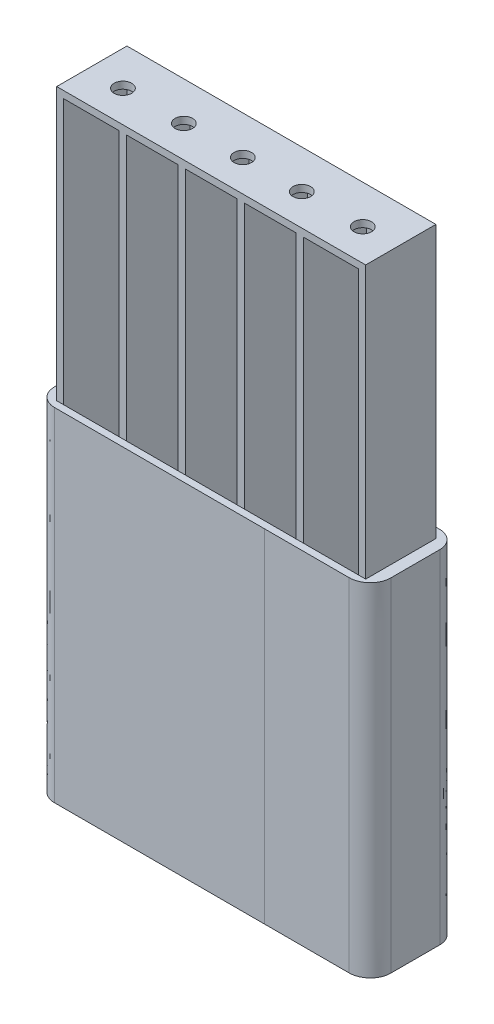
SolidWorks part; units mm, degrees
ref_plane "Front Plane" through (0, 0, 0) normal (0, 0, 1) x (1, 0, 0)
ref_plane "Top Plane" through (0, 0, 0) normal (0, 1, 0) x (1, 0, 0)
ref_plane "Right Plane" through (0, 0, 0) normal (1, 0, 0) x (0, 0, -1)
ref_plane "Plane1" through (0, 10, 0) normal (0, 1, 0) x (1, 0, 0)
sketch "Sketch1" plane through (0, 0, 0) normal (0, 0, 1) x (1, 0, 0)
  line L1 (-44, -87.5) -> (44, -87.5)
  line L2 (-44, -87.5) -> (-44, 87.5)
  line L3 (-44, 87.5) -> (44, 87.5)
  line L4 (44, -87.5) -> (44, 87.5)
  line L5 (-44, -87.5) -> (44, 87.5) construction
  line L6 (-44, 87.5) -> (44, -87.5) construction
  point P0 (0, 0)
  dimension "D1" = 88
  dimension "D2" = 175
extrude "Boss-Extrude1" add sketch "Sketch1" along normal blind 2
sketch "Sketch2" plane through (0, 0, 2) normal (0, 0, 1) x (1, 0, 0)
  line L4 (44, -87.5) -> (44, 87.5)
  line L5 (44, 87.5) -> (-44, 87.5)
  line L6 (-44, 87.5) -> (-44, -87.5)
  line L7 (-44, -87.5) -> (44, -87.5)
  line L8 (44, -87.5) -> (44, 87.5)
  line L9 (44, 87.5) -> (-44, 87.5)
  line L10 (-44, 87.5) -> (-44, -87.5)
  line L11 (-44, -87.5) -> (44, -87.5)
  dimension "D1" = 0
extrude "Extrude-Thin1" add sketch "Sketch2" along normal blind 18 thin thin type one direction reverse wall 2
sketch "Sketch7" plane through (0, 10, 0) normal (0, -1, 0) x (1, 0, 0)
  line L5 (-42.729, -2.8181) -> (42.1989, -2.8181)
  line L6 (47.2701, 2.1175) -> (47.2701, 16.0931)
  line L7 (41.1907, 22.0001) -> (17.1675, 21.99)
  line L8 (17.1675, 21.99) -> (-42.6899, 21.98)
  line L9 (-47.7299, 16.9812) -> (-47.7299, 2.1519)
  line L10 (-42.729, -2.8181) -> (42.1989, -2.8181)
  line L11 (47.2701, 2.1175) -> (47.2701, 16.0931)
  line L12 (41.1907, 22.0001) -> (17.1675, 21.99)
  line L13 (17.1675, 21.99) -> (-42.6899, 21.98)
  line L14 (-47.7299, 16.9812) -> (-47.7299, 2.1519)
  spline S4 degree 3 poles (-197.9292, 967.9227) (-37.6257, 170.0029) (18.1252, -7.458) (43.4954, -2.6664) (43.8136, -2.5749) (44.4247, -2.3335) (44.715, -2.1853) (45.2651, -1.8341) (45.5273, -1.6283) (45.9993, -1.1755) (46.2111, -0.9281) (46.4919, -0.5246) (46.5797, -0.3838) (46.7394, -0.0962) (46.8114, 0.0506) (47.0046, 0.5001) (47.1031, 0.8115) (53.1934, 30.3136) (-212.4086, 92.7702) (-718.1247, -641.4333) knots -9.650491 -9.650491 -9.650491 -9.650491 0.125 0.125 0.25 0.25 0.375 0.375 0.5 0.5 0.625 0.625 0.6875 0.6875 0.75 0.75 0.875 0.875 12.141398 12.141398 12.141398 12.141398 only from (42.1989, -2.8181) to (47.2701, 2.1175)
  spline S5 degree 3 poles (-921.5937, -231.4959) (-135.954, -70.0769) (52.7009, -9.9346) (47.1133, 17.4531) (47.0646, 17.6429) (46.9471, 18.0191) (46.8783, 18.2055) (46.6465, 18.7468) (46.4572, 19.0884) (46.1218, 19.5723) (46.0005, 19.7296) (45.7445, 20.0293) (45.6098, 20.1718) (45.1864, 20.5775) (44.8786, 20.8194) (44.2107, 21.2451) (43.8613, 21.4222) (43.1338, 21.7084) (42.7522, 21.8183) (5.7206, 28.7806) (-70.2801, -290.5664) (-187.4885, -951.498) knots -8.753519 -8.753519 -8.753519 -8.753519 0.125 0.125 0.1875 0.1875 0.25 0.25 0.375 0.375 0.4375 0.4375 0.5 0.5 0.625 0.625 0.75 0.75 0.875 0.875 12.708397 12.708397 12.708397 12.708397 only from (47.2701, 16.0931) to (41.1907, 22.0001)
  spline S6 degree 3 poles (193.8773, -949.635) (30.8282, -132.4012) (-20.3115, 26.4663) (-43.8283, 21.8535) (-43.9874, 21.8143) (-44.3027, 21.72) (-44.4596, 21.6646) (-44.9163, 21.4778) (-45.2053, 21.3253) (-45.7525, 20.9647) (-46.0122, 20.7545) (-46.4782, 20.2945) (-46.6874, 20.0434) (-46.9647, 19.6344) (-47.0511, 19.4923) (-47.2077, 19.2032) (-47.2785, 19.0556) (-47.4684, 18.6038) (-47.5657, 18.2894) (-53.7533, -12.2904) (224.8389, -73.2836) (932.5497, -180.6044) knots -8.978367 -8.978367 -8.978367 -8.978367 0.125 0.125 0.1875 0.1875 0.25 0.25 0.375 0.375 0.5 0.5 0.625 0.625 0.6875 0.6875 0.75 0.75 0.875 0.875 12.5333 12.5333 12.5333 12.5333 only from (-42.6899, 21.98) to (-47.7299, 16.9812)
  spline S7 degree 3 poles (2888.4957, 612.4469) (339.4184, 141.7364) (-54.8433, 37.3343) (-47.6023, 1.0211) (-47.5627, 0.8632) (-47.4674, 0.5501) (-47.4115, 0.3946) (-47.223, -0.0576) (-47.0692, -0.3435) (-46.7057, -0.8843) (-46.4943, -1.14) (-46.0325, -1.5978) (-45.7806, -1.8031) (-45.2337, -2.1653) (-44.9433, -2.3186) (-44.3425, -2.5649) (-44.028, -2.6596) (8.2756, -12.954) (153.5093, 800.8807) (450.4105, 2954.9966) knots -14.064879 -14.064879 -14.064879 -14.064879 0.125 0.125 0.1875 0.1875 0.25 0.25 0.375 0.375 0.5 0.5 0.625 0.625 0.75 0.75 0.875 0.875 21.050483 21.050483 21.050483 21.050483 only from (-47.7299, 2.1519) to (-42.729, -2.8181)
  spline S8 degree 3 poles (42.1989, -2.8181) (42.5294, -2.8181) (42.8548, -2.7874) (43.4954, -2.6664) (43.8136, -2.5749) (44.4247, -2.3335) (44.715, -2.1853) (45.2651, -1.8341) (45.5273, -1.6283) (45.9993, -1.1755) (46.2111, -0.9281) (46.4919, -0.5246) (46.5797, -0.3838) (46.7394, -0.0962) (46.8114, 0.0506) (47.0046, 0.5001) (47.1031, 0.8115) (47.2367, 1.4589) (47.2701, 1.7868) (47.2701, 2.1175) knots 0 0 0 0 0.125 0.125 0.25 0.25 0.375 0.375 0.5 0.5 0.625 0.625 0.6875 0.6875 0.75 0.75 0.875 0.875 1 1 1 1
  spline S9 degree 3 poles (47.2701, 16.0931) (47.2701, 16.4893) (47.2305, 16.8787) (47.1133, 17.4531) (47.0646, 17.6429) (46.9471, 18.0191) (46.8783, 18.2055) (46.6465, 18.7468) (46.4572, 19.0884) (46.1218, 19.5723) (46.0005, 19.7296) (45.7445, 20.0293) (45.6098, 20.1718) (45.1864, 20.5775) (44.8786, 20.8194) (44.2107, 21.2451) (43.8613, 21.4222) (43.1338, 21.7084) (42.7522, 21.8183) (41.978, 21.9638) (41.5865, 22.0002) (41.1907, 22.0001) knots 0 0 0 0 0.125 0.125 0.1875 0.1875 0.25 0.25 0.375 0.375 0.4375 0.4375 0.5 0.5 0.625 0.625 0.75 0.75 0.875 0.875 1 1 1 1
  spline S10 degree 3 poles (-42.6899, 21.98) (-43.0213, 21.98) (-43.3473, 21.9479) (-43.8283, 21.8535) (-43.9874, 21.8143) (-44.3027, 21.72) (-44.4596, 21.6646) (-44.9163, 21.4778) (-45.2053, 21.3253) (-45.7525, 20.9647) (-46.0122, 20.7545) (-46.4782, 20.2945) (-46.6874, 20.0434) (-46.9647, 19.6344) (-47.0511, 19.4923) (-47.2077, 19.2032) (-47.2785, 19.0556) (-47.4684, 18.6038) (-47.5657, 18.2894) (-47.697, 17.6406) (-47.7299, 17.3127) (-47.7299, 16.9812) knots 0 0 0 0 0.125 0.125 0.1875 0.1875 0.25 0.25 0.375 0.375 0.5 0.5 0.625 0.625 0.6875 0.6875 0.75 0.75 0.875 0.875 1 1 1 1
  spline S11 degree 3 poles (-47.7299, 2.1519) (-47.7299, 1.8226) (-47.6975, 1.4989) (-47.6023, 1.0211) (-47.5627, 0.8632) (-47.4674, 0.5501) (-47.4115, 0.3946) (-47.223, -0.0576) (-47.0692, -0.3435) (-46.7057, -0.8843) (-46.4943, -1.14) (-46.0325, -1.5978) (-45.7806, -1.8031) (-45.2337, -2.1653) (-44.9433, -2.3186) (-44.3425, -2.5649) (-44.028, -2.6596) (-43.3839, -2.7864) (-43.0583, -2.8181) (-42.729, -2.8181) knots 0 0 0 0 0.125 0.125 0.1875 0.1875 0.25 0.25 0.375 0.375 0.5 0.5 0.625 0.625 0.75 0.75 0.875 0.875 1 1 1 1
  dimension "D1" = 0
extrude "Boss-Extrude2" add sketch "Sketch7" along normal up to surface (97.5 mm away) up to face at (0, -87.5, 10)
sketch "Sketch10" plane through (0, 0, 2) normal (0, 0, -1) x (-1, 0, 0)
  line L8 (42, -85.5) -> (42, 85.5)
  line L9 (-42, -85.5) -> (42, -85.5)
  line L10 (-42, 85.5) -> (-42, -85.5)
  line L11 (42, 85.5) -> (-42, 85.5)
extrude "Cut-Extrude2" cut sketch "Sketch10" against normal up to surface (18 mm away) up to face at (0, 48.25, 20)
sketch "Sketch3" plane through (0, 0, 2) normal (0, 0, 1) x (1, 0, 0)
  line L0 (-25.2, 85.5) -> (-25.2, -85.5)
  line L1 (42, 85.5) -> (-42, 85.5) construction
  line L2 (-42, -85.5) -> (42, -85.5) construction
  line L3 (-8.4, 85.5) -> (-8.4, -85.5)
  line L4 (42, 85.5) -> (-42, 85.5) construction
  line L5 (25.2, 85.5) -> (25.2, -85.5)
  line L6 (8.4, 85.5) -> (8.4, -85.5)
  line L7 (-42, -85.5) -> (42, -85.5) construction
  line L8 (-42, 85.5) -> (-42, -85.5) construction
  line L9 (42, -85.5) -> (42, 85.5) construction
  point P20 (0, 0)
  dimension "D1" = 16.8
  dimension "D2" = 16.8
  dimension "D3" = 16.8
  dimension "D4" = 16.8
  dimension "D5" = 16.8
extrude "Extrude-Thin2" add sketch "Sketch3" along normal blind 18 thin thin type mid plane wall 2.2
sketch "Sketch4" plane through (0, 87.5, 0) normal (0, 1, 0) x (1, 0, 0)
  line L0 (26.3, -20) -> (26.3, -2) construction
  line L1 (26.3, -2) -> (42, -2) construction
  line L2 (42, -2) -> (42, -20) construction
  line L3 (42, -20) -> (26.3, -20) construction
  line L4 (9.5, -20) -> (9.5, -2) construction
  line L5 (9.5, -2) -> (24.1, -2) construction
  line L6 (24.1, -2) -> (24.1, -20) construction
  line L7 (24.1, -20) -> (9.5, -20) construction
  line L8 (-7.3, -2) -> (7.3, -2) construction
  line L9 (7.3, -2) -> (7.3, -20) construction
  line L10 (7.3, -20) -> (-7.3, -20) construction
  line L11 (-7.3, -20) -> (-7.3, -2) construction
  line L12 (-24.1, -2) -> (-9.5, -2) construction
  line L13 (-9.5, -2) -> (-9.5, -20) construction
  line L14 (-9.5, -20) -> (-24.1, -20) construction
  line L15 (-24.1, -20) -> (-24.1, -2) construction
  line L16 (-42, -2) -> (-26.3, -2) construction
  line L17 (-26.3, -2) -> (-26.3, -20) construction
  line L18 (-26.3, -20) -> (-42, -20) construction
  line L19 (-42, -20) -> (-42, -2) construction
  line L20 (26.3, -20) -> (26.3, -2) construction
  line L21 (26.3, -2) -> (42, -2) construction
  line L22 (42, -2) -> (42, -20) construction
  line L23 (42, -20) -> (26.3, -20) construction
  line L24 (9.5, -20) -> (9.5, -2) construction
  line L25 (9.5, -2) -> (24.1, -2) construction
  line L26 (24.1, -2) -> (24.1, -20) construction
  line L27 (24.1, -20) -> (9.5, -20) construction
  line L28 (-7.3, -2) -> (7.3, -2) construction
  line L29 (7.3, -2) -> (7.3, -20) construction
  line L30 (7.3, -20) -> (-7.3, -20) construction
  line L31 (-7.3, -20) -> (-7.3, -2) construction
  line L32 (-24.1, -2) -> (-9.5, -2) construction
  line L33 (-9.5, -2) -> (-9.5, -20) construction
  line L34 (-9.5, -20) -> (-24.1, -20) construction
  line L35 (-24.1, -20) -> (-24.1, -2) construction
  line L36 (-42, -2) -> (-26.3, -2) construction
  line L37 (-26.3, -2) -> (-26.3, -20) construction
  line L38 (-26.3, -20) -> (-42, -20) construction
  line L39 (-42, -20) -> (-42, -2) construction
  line L40 (42, -11) -> (-42, -11) construction
  line L41 (-16.8, -20) -> (-16.8, -2) construction
  line L42 (-34.15, -20) -> (-34.15, -2) construction
  line L43 (0, -20) -> (0, -2) construction
  line L44 (16.8, -20) -> (16.8, -2) construction
  line L45 (34.15, -20) -> (34.15, -2) construction
  point P26 (34.15, -11)
  point P28 (16.8, -11)
  point P30 (0, -11)
  point P31 (-16.8, -11)
  point P34 (-34.15, -11)
hole_wizard "Ø5.0mm Dowel Hole3" positions "Sketch5" profile "Sketch6" hole size "Ø5.0" standard "BSI" end condition up to next
sketch "Sketch5" plane through (0, 87.5, 0) normal (0, 1, 0) x (1, 0, 0)
  line L0 (-34.15, -20) -> (-34.15, -2) construction
  line L1 (-16.8, -20) -> (-16.8, -2) construction
  point P0 (-34.15, -11)
  point P4 (-16.8, -11)
  point P8 (0, -11)
  point P11 (16.8, -11)
  point P14 (34.15, -11)
sketch "Sketch6" plane through (-34.15, 87.5, 11) normal (1, 0, 0) x (0, 0, 1)
  line L0 (0, 0) -> (0, 2)
  line L1 (0, 2) -> (2.5, 2)
  line L2 (2.5, 2) -> (2.5, 0)
  line L5 (2.5, 0) -> (0, 0)
  line L11 (0, -6.35) -> (0, 107.95) construction
  dimension "Thru Hole Dia." = 5
  dimension "Thru Hole Depth" = 2
